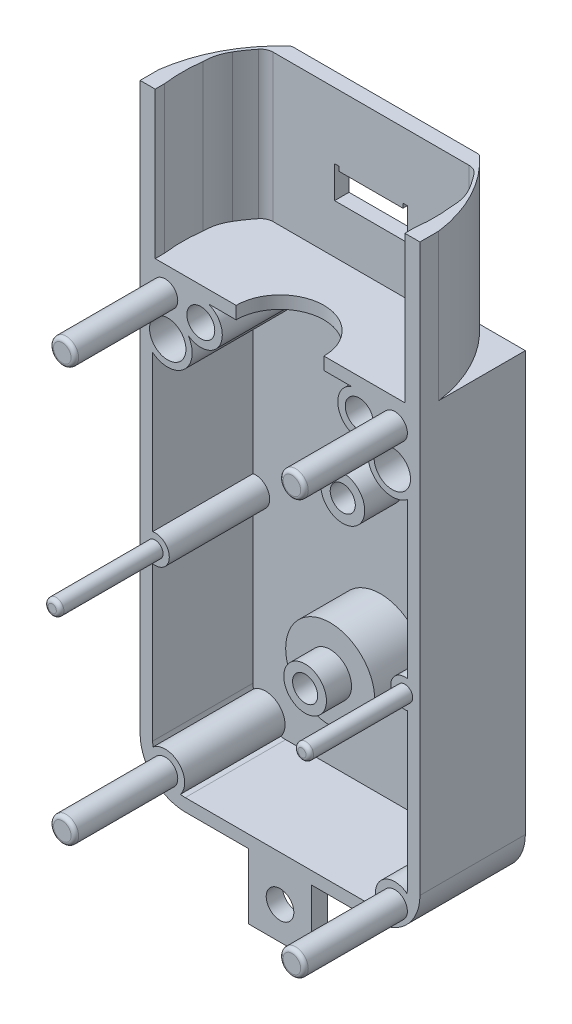
SolidWorks part; units mm, degrees
ref_plane "Front Plane" through (0, 0, 0) normal (0, 0, 1) x (1, 0, 0)
ref_plane "Top Plane" through (0, 0, 0) normal (0, 1, 0) x (1, 0, 0)
ref_plane "Right Plane" through (0, 0, 0) normal (1, 0, 0) x (0, 0, -1)
sketch "Sketch1" plane through (0, 0, 0) normal (0, 0, 1) x (1, 0, 0)
  line L0 (-9.95, -18.5) -> (-9.95, -1.55) construction
  line L1 (-7.55, -18.5) -> (7.55, -18.5)
  line L2 (-11.15, -14.9) -> (-11.15, 18.5)
  line L3 (-11.15, 18.5) -> (11.15, 18.5)
  line L4 (11.15, -14.9) -> (11.15, 18.5)
  line L5 (-11.15, -18.5) -> (11.15, 18.5) construction
  line L6 (-11.15, 18.5) -> (11.15, -18.5) construction
  line L7 (9.15, -18.5) -> (9.15, -16.5) construction
  line L8 (0, -18.5) -> (0, -7.2) construction
  line L9 (0, 0) -> (5.3483, 0)
  line L10 (8.95, 13.4566) -> (11.15, 13.4566)
  circle A0 centre (9.15, -16.5) radius 1
  circle A1 centre (-9.95, -1.55) radius 0.625
  circle A2 centre (9.95, -1.55) radius 0.625
  circle A3 centre (-9.15, -16.5) radius 1
  circle A4 centre (0, -7.2) radius 2.7
  circle A5 centre (9.15, 16.5) radius 1
  circle A6 centre (-9.15, 16.5) radius 1
  circle A7 centre (8.95, 13.4566) radius 1.45
  circle A8 centre (6.3127, 15.9) radius 1.1123
  circle A9 centre (-6.3127, 15.9) radius 1.1123
  circle A10 centre (-8.95, 13.4566) radius 1.45
  arc A11 (-11.15, -14.9) -> (-7.55, -18.5) centre (-7.55, -14.9) ccw
  arc A12 (11.15, -14.9) -> (7.55, -18.5) centre (7.55, -14.9) cw
  point P0 (0, 0)
  dimension "D7" = 2
  dimension "D8" = 1.25
  dimension "D10" = 5.4
  dimension "D12" = 2.9
  dimension "D13" = 2
  dimension "D17" = 3.6
  dimension "D1" = 22.3
  dimension "D2" = 37
  dimension "D3" = 16.95
  dimension "D4" = 1.2
  dimension "D5" = 2
  dimension "D6" = 2
  dimension "D9" = 11.3
  dimension "D11" = 2.2
  dimension "D14" = 3.05
  dimension "D15" = 2.6
  dimension "D16" = 2.9
extrude "Boss-Extrude1" add sketch "Sketch1" along normal blind 1 contours A12 L4 A7 L3 L2 A11 L1 A9 A8 A6 A3 A0 A1 A2 A4 A5 A10 region at (0, -0.045, 0)
sketch "Sketch2" plane through (0, 0, 0) normal (0, 0, 1) x (1, 0, 0)
  line L0 (0, 18.5) -> (0, 11.4842) construction
  line L1 (-11.15, 18.5) -> (11.15, 18.5) construction
  line L2 (-11.15, -14.9) -> (-11.15, 18.5) construction
  line L3 (11.15, -14.9) -> (11.15, 18.5) construction
  line L4 (-7.55, -18.5) -> (7.55, -18.5) construction
  line L5 (-11.15, -14.9) -> (-11.15, 18.5)
  line L6 (-11.15, 18.5) -> (11.15, 18.5)
  line L7 (11.15, -14.9) -> (11.15, 18.5)
  line L8 (-7.55, -18.5) -> (7.55, -18.5)
  line L9 (-10.15, -14.9) -> (-10.15, -2.6571)
  line L10 (-10.15, -0.4429) -> (-10.15, 11.9195)
  line L11 (10.15, -14.9) -> (10.15, -2.6571)
  line L12 (-7.55, -17.5) -> (7.55, -17.5)
  line L13 (10.15, -14.9) -> (10.15, 17.5) construction
  line L14 (-10.15, -14.9) -> (-10.15, 17.5) construction
  line L15 (-5.7028, 17.5) -> (5.7028, 17.5)
  line L16 (-10.15, 17.5) -> (10.15, 17.5) construction
  line L17 (10.15, -0.4429) -> (10.15, 11.9195)
  arc A0 (-7.9413, -17.4704) -> (-10.1204, -15.2913) centre (-9.15, -16.5) ccw
  circle A1 centre (-6.3127, 15.9) radius 1.1123 construction
  circle A2 centre (-6.3127, 15.9) radius 1.7123
  arc A3 (-7.3059, 14.5051) -> (-5.7028, 17.5) centre (-6.3127, 15.9) ccw
  circle A4 centre (-6.3127, 15.9) radius 1.1123
  circle A5 centre (-8.95, 13.4566) radius 1.45 construction
  circle A6 centre (-8.95, 13.4566) radius 1.45
  arc A7 (-10.15, 11.9195) -> (-7.3059, 14.5051) centre (-8.95, 13.4566) ccw
  circle A8 centre (-9.95, -1.55) radius 0.625 construction
  circle A9 centre (-9.95, -1.55) radius 0.625
  arc A10 (-10.15, -2.6571) -> (-10.15, -0.4429) centre (-9.95, -1.55) ccw
  circle A11 centre (-9.15, -16.5) radius 1 construction
  circle A12 centre (-9.15, -16.5) radius 1
  circle A13 centre (9.15, -16.5) radius 1
  circle A15 centre (9.95, -1.55) radius 0.625
  arc A16 (10.15, -2.6571) -> (10.15, -0.4429) centre (9.95, -1.55) cw
  circle A17 centre (8.95, 13.4566) radius 1.45
  arc A18 (10.15, 11.9195) -> (7.3059, 14.5051) centre (8.95, 13.4566) cw
  circle A19 centre (6.3127, 15.9) radius 1.1123
  arc A20 (7.3059, 14.5051) -> (5.7028, 17.5) centre (6.3127, 15.9) cw
  arc A21 (7.55, -18.5) -> (11.15, -14.9) centre (7.55, -14.9) ccw construction
  arc A22 (-11.15, -14.9) -> (-7.55, -18.5) centre (-7.55, -14.9) ccw construction
  arc A23 (7.55, -18.5) -> (11.15, -14.9) centre (7.55, -14.9) ccw
  arc A24 (-11.15, -14.9) -> (-7.55, -18.5) centre (-7.55, -14.9) ccw
  arc A25 (7.55, -17.5) -> (7.9413, -17.4704) centre (7.55, -14.9) ccw
  arc A26 (-10.15, -14.9) -> (-10.1204, -15.2913) centre (-7.55, -14.9) ccw
  circle A27 centre (-8.95, 13.4566) radius 1.95 construction
  circle A28 centre (-9.15, 16.5) radius 1 construction
  circle A29 centre (-9.15, 16.5) radius 1
  circle A30 centre (9.15, 16.5) radius 1 construction
  circle A31 centre (9.15, 16.5) radius 1
  circle A32 centre (-9.95, -1.55) radius 1.125 construction
  circle A33 centre (-9.15, -16.5) radius 1.55 construction
  arc A34 (-7.9413, -17.4704) -> (-7.55, -17.5) centre (-7.55, -14.9) ccw
  arc A35 (-10.15, -14.9) -> (-7.55, -17.5) centre (-7.55, -14.9) ccw construction
  arc A36 (10.1204, -15.2913) -> (10.15, -14.9) centre (7.55, -14.9) ccw
  arc A37 (7.55, -17.5) -> (10.15, -14.9) centre (7.55, -14.9) ccw construction
  arc A38 (7.9413, -17.4704) -> (10.1204, -15.2913) centre (9.15, -16.5) cw
  dimension "D1" = 0.6
  dimension "D2" = 0.5
  dimension "D3" = 0.5
  dimension "D4" = 0.55
  dimension "D5" = 1
extrude "Boss-Extrude2" add sketch "Sketch2" along normal blind 9.9
sketch "Sketch3" plane through (0, 0, 1) normal (0, 0, 1) x (1, 0, 0)
  line L0 (5.7028, 17.5) -> (-5.7028, 17.5) construction
  line L1 (5.7028, 17.5) -> (4.3272, 17.5)
  line L2 (-4.3272, 17.5) -> (-5.7028, 17.5)
  arc A0 (-7, 13.4444) -> (-4.3272, 17.5) centre (-6.3127, 15.9) ccw
  arc A1 (4.3272, 17.5) -> (7, 13.4444) centre (6.3127, 15.9) ccw
  arc A2 (-7.3059, 14.5051) -> (-5.7028, 17.5) centre (-6.3127, 15.9) ccw construction
  arc A3 (-7.3059, 14.5051) -> (-5.7028, 17.5) centre (-6.3127, 15.9) ccw
  arc A4 (-10.15, 11.9195) -> (-7.3059, 14.5051) centre (-8.95, 13.4566) ccw construction
  arc A5 (-7, 13.4444) -> (-7.3059, 14.5051) centre (-8.95, 13.4566) ccw
  arc A6 (5.7028, 17.5) -> (7.3059, 14.5051) centre (6.3127, 15.9) ccw construction
  arc A7 (5.7028, 17.5) -> (7.3059, 14.5051) centre (6.3127, 15.9) ccw
  arc A8 (7.3059, 14.5051) -> (10.15, 11.9195) centre (8.95, 13.4566) ccw construction
  arc A9 (7.3059, 14.5051) -> (7, 13.4444) centre (8.95, 13.4566) ccw
  dimension "D1" = 5.1
  dimension "D2" = 5.1
extrude "Boss-Extrude3" add sketch "Sketch3" along normal blind 1.55
sketch "Sketch4" plane through (0, 0, 0) normal (0, 0, -1) x (-1, 0, 0)
  line L0 (0, 18.5) -> (0, 14.3921) construction
  line L1 (11.15, 18.5) -> (-11.15, 18.5) construction
  circle A0 centre (-6.3127, 15.9) radius 2.2
  circle A1 centre (6.3127, 15.9) radius 2.2
  dimension "D1" = 4.4
extrude "Cut-Extrude1" cut sketch "Sketch4" against normal blind 2.1
sketch "Sketch5" plane through (0, 0, 0) normal (0, 0, -1) x (-1, 0, 0)
  circle A0 centre (0, -7.2) radius 3.55
  circle A1 centre (0, -7.2) radius 2.7 construction
  circle A2 centre (0, -7.2) radius 2.7
  dimension "D1" = 7.1
extrude "Boss-Extrude4" add sketch "Sketch5" along normal blind 0.8
sketch "Sketch6" plane through (0, 0, 0) normal (0, 0, -1) x (-1, 0, 0)
  circle A0 centre (0, 4.45) radius 2.05
extrude "Boss-Extrude5" add sketch "Sketch6" along normal blind 2.4
sketch "Sketch7" plane through (0, 0, 9.9) normal (0, 0, 1) x (1, 0, 0)
  line L0 (-7.55, -18.5) -> (7.55, -18.5) construction
  line L1 (-2.5, -18.5) -> (2.5, -18.5)
  line L3 (-2.5, -18.5) -> (-2.5, -23.7)
  line L4 (-2.5, -23.7) -> (2.5, -23.7)
  line L5 (2.5, -18.5) -> (2.5, -23.7)
  circle A0 centre (0, -21.1) radius 1.1
  point P0 (0, -18.5)
  point P1 (0, -18.5)
  dimension "D2" = 2.2
  dimension "D1" = 5
extrude "Boss-Extrude6" add sketch "Sketch7" against normal blind 1.3
sketch "Sketch8" plane through (0, 18.5, 0) normal (0, 1, 0) x (1, 0, 0)
  line L0 (11.15, -9.9) -> (-11.15, -9.9) construction
  line L1 (3.5, -9.9) -> (-3.5, -9.9)
  arc A0 (3.5, -9.9) -> (-3.5, -9.9) centre (0, -9.9) ccw
  dimension "D1" = 7
extrude "Cut-Extrude2" cut sketch "Sketch8" against normal blind 1.3
sketch "Sketch9" plane through (0, 18.5, 0) normal (0, 1, 0) x (1, 0, 0)
  line L0 (-2.5, -9.9) -> (2.5, -9.9) construction
  line L1 (-9.95, -9.9) -> (-9.95, -9.1592)
  line L2 (9.95, -9.9) -> (9.95, -9.1592)
  line L3 (11.15, -9.9) -> (3.5, -9.9) construction
  line L4 (7.4835, -1.5) -> (-7.4835, -1.5)
  line L5 (0, -9.9) -> (0, -4.9263) construction
  line L6 (11.15, -9.9) -> (9.95, -9.9)
  line L7 (-9.95, -9.9) -> (-11.15, -9.9)
  line L8 (7.8062, -2.65) -> (-7.8062, -2.65)
  line L9 (11.15, -9.9) -> (11.15, 0) construction
  line L10 (11.15, -9.9) -> (11.15, -8.4033)
  line L11 (-11.15, -9.9) -> (-11.15, 0) construction
  line L12 (-11.15, -9.9) -> (-11.15, -8.4033)
  arc A0 (11.15, -8.4033) -> (7.4835, -1.5) centre (0, -9.9) ccw
  arc A1 (9.4392, -4.2518) -> (8.5869, -3.025) centre (0, -9.9) ccw
  arc A2 (-7.4835, -1.5) -> (-11.15, -8.4033) centre (0, -9.9) ccw
  arc A3 (-8.5869, -3.025) -> (-9.4392, -4.2518) centre (0, -9.9) ccw
  arc A4 (-9.95, -6.1003) -> (-9.4392, -4.2518) centre (-6.35, -6.1003) cw
  arc A5 (9.95, -6.1003) -> (9.4392, -4.2518) centre (6.35, -6.1003) ccw
  arc A6 (-7.8062, -2.65) -> (-8.5869, -3.025) centre (-7.8062, -3.65) ccw
  arc A7 (7.8062, -2.65) -> (8.5869, -3.025) centre (7.8062, -3.65) cw
  arc A8 (9.95, -9.1592) -> (9.95, -6.1003) centre (-2.0177, -7.6298) ccw
  arc A9 (-9.95, -9.1592) -> (-9.95, -6.1003) centre (2.0177, -7.6298) cw
  point P2 (0, -9.9)
  point P28 (-8.2727, -2.65)
  dimension "D3" = 1.2
  dimension "D2" = 22
  dimension "D4" = 3.6
  dimension "D5" = 1
  dimension "D6" = 24.13
  dimension "D1" = 0
extrude "Boss-Extrude7" add sketch "Sketch9" along normal blind 11.7
sketch "Sketch10" plane through (0, 0, 2.65) normal (0, 0, 1) x (1, 0, 0)
  line L2 (0, 24.6) -> (0, 22.4) construction
  line L3 (2.55, 24.6) -> (-2.55, 24.6)
  line L4 (2.9, 24.6) -> (2.9, 22.4)
  line L5 (2.9, 22.4) -> (-2.9, 22.4)
  line L6 (-2.9, 24.6) -> (-2.9, 22.4)
  line L7 (2.9, 24.6) -> (-2.9, 22.4) construction
  line L8 (2.9, 22.4) -> (-2.9, 24.6) construction
  line L10 (2.55, 24.6) -> (2.55, 24.95)
  line L12 (-2.55, 24.6) -> (-2.55, 24.95)
  line L13 (2.55, 24.0735) -> (0, 24.6) construction
  line L15 (-2.9, 24.95) -> (-2.55, 24.95)
  line L17 (-2.9, 24.95) -> (-2.9, 24.6)
  line L18 (2.9, 24.95) -> (2.9, 24.6)
  line L19 (2.55, 24.95) -> (2.9, 24.95)
  line L20 (0, 24.6) -> (-2.55, 24.0735) construction
  point P0 (0, 23.5)
extrude "Cut-Extrude3" cut sketch "Sketch10" against normal blind 1.7
sketch "Sketch11" plane through (0, 0, 1.5) normal (0, 0, -1) x (-1, 0, 0)
  line L1 (2.55, 24.6) -> (-2.55, 24.6)
  line L2 (2.55, 24.6) -> (2.55, 26.2)
  line L3 (2.55, 26.2) -> (-2.55, 26.2)
  line L4 (-2.55, 24.6) -> (-2.55, 26.2)
  dimension "D1" = 1.6
extrude "Boss-Extrude8" add sketch "Sketch11" along normal blind 3
sketch "Sketch12" plane through (0, 26.2, 0) normal (0, 1, 0) x (1, 0, 0)
  line L0 (-2.55, 1.5) -> (-2.55, -1.5) construction
  line L1 (2.55, 1.5) -> (-2.55, 1.5)
  line L2 (2.55, 1.5) -> (2.55, 0.5)
  line L3 (2.55, 0.5) -> (-2.55, 0.5)
  line L4 (-2.55, 1.5) -> (-2.55, 0.5)
  dimension "D1" = 1
extrude "Boss-Extrude9" add sketch "Sketch12" against normal blind 2.5
sketch "Sketch13" plane through (0, 0, 1) normal (0, 0, 1) x (1, 0, 0)
  circle A2 centre (0, 4.45) radius 1
  dimension "D1" = 2
extrude "Cut-Extrude4" cut sketch "Sketch13" against normal blind 2.5
fillet "Fillet1" radius 0.3 1 edges at (-2.05, 4.45, -2.4)
fillet "Fillet2" radius 0.3 2 edges at (7.4835, 24.35, 1.5) (-7.4835, 24.35, 1.5)
sketch "Sketch15" plane through (-10.15, 0, 0) normal (1, 0, 0) x (0, 0, -1)
  line L0 (-9.9, -8.7785) -> (-1.9, -8.7785)
  line L1 (-9.9, -2.6571) -> (-9.9, -14.9) construction
  dimension "D1" = 8
sketch "Sketch16" plane through (0, 0, 1) normal (0, 0, 1) x (1, 0, 0)
  line L6 (4.3272, 17.5) -> (-4.3272, 17.5)
  line L7 (-10.15, 11.9195) -> (-10.15, -0.4429)
  line L8 (-10.15, -2.6571) -> (-10.15, -14.9)
  line L9 (-7.55, -17.5) -> (7.55, -17.5)
  line L10 (10.15, -14.9) -> (10.15, -2.6571)
  line L11 (10.15, -0.4429) -> (10.15, 11.9195)
  line L12 (4.3272, 17.5) -> (-4.3272, 17.5)
  line L13 (-10.15, 11.9195) -> (-10.15, -0.4429)
  line L14 (-10.15, -2.6571) -> (-10.15, -14.9)
  line L15 (-7.55, -17.5) -> (7.55, -17.5)
  line L16 (10.15, -14.9) -> (10.15, -2.6571)
  line L17 (10.15, -0.4429) -> (10.15, 11.9195)
  arc A12 (-7, 13.4444) -> (-4.3272, 17.5) centre (-6.3127, 15.9) ccw
  arc A13 (-10.15, 11.9195) -> (-7, 13.4444) centre (-8.95, 13.4566) ccw
  arc A14 (-10.15, -2.6571) -> (-10.15, -0.4429) centre (-9.95, -1.55) ccw
  arc A15 (-10.15, -14.9) -> (-10.1204, -15.2913) centre (-7.55, -14.9) ccw
  arc A16 (-7.9413, -17.4704) -> (-10.1204, -15.2913) centre (-9.15, -16.5) ccw
  arc A17 (-7.9413, -17.4704) -> (-7.55, -17.5) centre (-7.55, -14.9) ccw
  arc A18 (7.55, -17.5) -> (7.9413, -17.4704) centre (7.55, -14.9) ccw
  arc A19 (10.1204, -15.2913) -> (7.9413, -17.4704) centre (9.15, -16.5) ccw
  arc A20 (10.1204, -15.2913) -> (10.15, -14.9) centre (7.55, -14.9) ccw
  arc A21 (10.15, -0.4429) -> (10.15, -2.6571) centre (9.95, -1.55) ccw
  arc A22 (7, 13.4444) -> (10.15, 11.9195) centre (8.95, 13.4566) ccw
  arc A23 (4.3272, 17.5) -> (7, 13.4444) centre (6.3127, 15.9) ccw
  arc A24 (-7, 13.4444) -> (-4.3272, 17.5) centre (-6.3127, 15.9) ccw
  arc A25 (-10.15, 11.9195) -> (-7, 13.4444) centre (-8.95, 13.4566) ccw
  arc A26 (-10.15, -2.6571) -> (-10.15, -0.4429) centre (-9.95, -1.55) ccw
  arc A27 (-10.15, -14.9) -> (-10.1204, -15.2913) centre (-7.55, -14.9) ccw
  arc A28 (-7.9413, -17.4704) -> (-10.1204, -15.2913) centre (-9.15, -16.5) ccw
  arc A29 (-7.9413, -17.4704) -> (-7.55, -17.5) centre (-7.55, -14.9) ccw
  arc A30 (7.55, -17.5) -> (7.9413, -17.4704) centre (7.55, -14.9) ccw
  arc A31 (10.1204, -15.2913) -> (7.9413, -17.4704) centre (9.15, -16.5) ccw
  arc A32 (10.1204, -15.2913) -> (10.15, -14.9) centre (7.55, -14.9) ccw
  arc A33 (10.15, -0.4429) -> (10.15, -2.6571) centre (9.95, -1.55) ccw
  arc A34 (7, 13.4444) -> (10.15, 11.9195) centre (8.95, 13.4566) ccw
  arc A35 (4.3272, 17.5) -> (7, 13.4444) centre (6.3127, 15.9) ccw
  dimension "D1" = 0
extrude "Boss-Extrude10" add sketch "Sketch16" along normal up to vertex (0.9 mm away) up to point (-10.15, -8.7785, 1.9)
sketch "Sketch17" plane through (0, 0, 2.1) normal (0, 0, -1) x (-1, 0, 0)
  arc A4 (8.2517, 16.9394) -> (8.5065, 15.7345) centre (9.15, 16.5) ccw
  arc A5 (8.2517, 16.9394) -> (7.7012, 14.1935) centre (6.3127, 15.9) ccw
  arc A6 (8.1201, 14.6456) -> (7.7012, 14.1935) centre (8.95, 13.4566) ccw
  arc A7 (8.1201, 14.6456) -> (8.5065, 15.7345) centre (6.3127, 15.9) ccw
  arc A8 (8.2517, 16.9394) -> (8.5065, 15.7345) centre (9.15, 16.5) ccw
  arc A9 (8.2517, 16.9394) -> (7.7012, 14.1935) centre (6.3127, 15.9) ccw
  arc A10 (8.1201, 14.6456) -> (7.7012, 14.1935) centre (8.95, 13.4566) ccw
  arc A11 (8.1201, 14.6456) -> (8.5065, 15.7345) centre (6.3127, 15.9) ccw
  arc A12 (-8.5065, 15.7345) -> (-8.2517, 16.9394) centre (-9.15, 16.5) ccw
  arc A13 (-8.5065, 15.7345) -> (-8.1201, 14.6456) centre (-6.3127, 15.9) ccw
  arc A14 (-7.7012, 14.1935) -> (-8.1201, 14.6456) centre (-8.95, 13.4566) ccw
  arc A15 (-7.7012, 14.1935) -> (-8.2517, 16.9394) centre (-6.3127, 15.9) ccw
  arc A16 (-8.5065, 15.7345) -> (-8.2517, 16.9394) centre (-9.15, 16.5) ccw
  arc A17 (-8.5065, 15.7345) -> (-8.1201, 14.6456) centre (-6.3127, 15.9) ccw
  arc A18 (-7.7012, 14.1935) -> (-8.1201, 14.6456) centre (-8.95, 13.4566) ccw
  arc A19 (-7.7012, 14.1935) -> (-8.2517, 16.9394) centre (-6.3127, 15.9) ccw
  dimension "D1" = 0
  dimension "D2" = 0
extrude "Boss-Extrude11" add sketch "Sketch17" along normal up to vertex up to point (-7.7012, 14.1935, 0)
sketch "Sketch18" plane through (0, 0, 2.55) normal (0, 0, 1) x (1, 0, 0)
  line L1 (-4.3272, 17.5) -> (-5.7028, 17.5)
  line L2 (-4.3272, 17.5) -> (-5.7028, 17.5)
  line L3 (5.7028, 17.5) -> (4.3272, 17.5)
  line L4 (5.7028, 17.5) -> (4.3272, 17.5)
  arc A3 (-7.3059, 14.5051) -> (-5.7028, 17.5) centre (-6.3127, 15.9) ccw
  arc A4 (-7, 13.4444) -> (-7.3059, 14.5051) centre (-8.95, 13.4566) ccw
  arc A5 (-7, 13.4444) -> (-4.3272, 17.5) centre (-6.3127, 15.9) ccw
  arc A6 (-7.3059, 14.5051) -> (-5.7028, 17.5) centre (-6.3127, 15.9) ccw
  arc A7 (-7, 13.4444) -> (-7.3059, 14.5051) centre (-8.95, 13.4566) ccw
  arc A8 (-7, 13.4444) -> (-4.3272, 17.5) centre (-6.3127, 15.9) ccw
  arc A9 (4.3272, 17.5) -> (7, 13.4444) centre (6.3127, 15.9) ccw
  arc A10 (7.3059, 14.5051) -> (7, 13.4444) centre (8.95, 13.4566) ccw
  arc A11 (5.7028, 17.5) -> (7.3059, 14.5051) centre (6.3127, 15.9) ccw
  arc A12 (4.3272, 17.5) -> (7, 13.4444) centre (6.3127, 15.9) ccw
  arc A13 (7.3059, 14.5051) -> (7, 13.4444) centre (8.95, 13.4566) ccw
  arc A14 (5.7028, 17.5) -> (7.3059, 14.5051) centre (6.3127, 15.9) ccw
  dimension "D1" = 0
  dimension "D2" = 0
extrude "Cut-Extrude5" cut sketch "Sketch18" against normal up to vertex up to point (-7, 13.4444, 1.9)
sketch "Sketch19" plane through (0, 18.5, 0) normal (0, 1, 0) x (1, 0, 0)
  line L0 (11.15, -8.4033) -> (11.15, 0) construction
  line L1 (-11.15, 3.5146) -> (11.15, 3.5146)
  line L2 (-11.15, 3.5146) -> (-11.15, -1.5)
  line L3 (-11.15, -1.5) -> (11.15, -1.5)
  line L4 (11.15, 3.5146) -> (11.15, -1.5)
extrude "Cut-Extrude7" cut sketch "Sketch19" against normal blind 37.5
sketch "Sketch20" plane through (0, 0, 1.5) normal (0, 0, -1) x (-1, 0, 0)
  circle A1 centre (0, -7.2) radius 2.7
  circle A2 centre (0, -7.2) radius 2.7
  circle A3 centre (0, -7.2) radius 3.55
  circle A4 centre (0, -7.2) radius 3.55
  dimension "D1" = 0
  dimension "D2" = 0
extrude "Boss-Extrude12" add sketch "Sketch20" against normal blind 4.4
sketch "Sketch21" plane through (0, 0, 1.5) normal (0, 0, -1) x (-1, 0, 0)
  circle A3 centre (0, -7.2) radius 2.7
  circle A4 centre (0, -7.2) radius 2.7
  dimension "D2" = 0
extrude "Cut-Extrude8" cut sketch "Sketch21" against normal blind 3.4
sketch "Sketch22" plane through (0, 0, 5.9) normal (0, 0, 1) x (1, 0, 0)
  circle A0 centre (0, -7.2) radius 1
  circle A1 centre (0, -7.2) radius 2.7 construction
  circle A2 centre (0, -7.2) radius 2.7
  dimension "D1" = 2
extrude "Boss-Extrude13" add sketch "Sketch22" against normal blind 1
sketch "Sketch23" plane through (0, 0, 5.9) normal (0, 0, 1) x (1, 0, 0)
  circle A0 centre (0, -7.2) radius 1 construction
  circle A1 centre (0, -7.2) radius 1
  circle A2 centre (0, -7.2) radius 1.7
  dimension "D1" = 3.4
extrude "Boss-Extrude14" add sketch "Sketch23" along normal blind 2
sketch "Sketch24" plane through (0, 0, 1.9) normal (0, 0, 1) x (1, 0, 0)
  circle A0 centre (0, 4.45) radius 1.75
  circle A1 centre (0, 4.45) radius 1
  circle A2 centre (0, 4.45) radius 1
  dimension "D2" = 3.5
  dimension "D1" = 0
extrude "Boss-Extrude15" add sketch "Sketch24" along normal blind 3
ref_plane "Plane1" through (0, 0, 8.9) normal (0, 0, 1) x (1, 0, 0)
sketch "Sketch26" plane through (0, 0, 8.9) normal (0, 0, 1) x (1, 0, 0)
  circle A0 centre (-9.15, 16.5) radius 1 construction
  circle A1 centre (-9.15, 16.5) radius 1
  circle A2 centre (9.15, 16.5) radius 1 construction
  circle A3 centre (9.15, 16.5) radius 1
  circle A4 centre (-9.95, -1.55) radius 0.625 construction
  circle A5 centre (-9.95, -1.55) radius 0.625
  circle A6 centre (9.95, -1.55) radius 0.625 construction
  circle A7 centre (9.95, -1.55) radius 0.625
  circle A8 centre (-9.15, -16.5) radius 1 construction
  circle A9 centre (-9.15, -16.5) radius 1
  circle A10 centre (9.15, -16.5) radius 1 construction
  circle A11 centre (9.15, -16.5) radius 1
extrude "Boss-Extrude16" add sketch "Sketch26" along normal blind 9.2
fillet "Fillet3" radius 0.3 6 edges at (10.15, -16.5, 18.1) (-8.15, -16.5, 18.1) (10.575, -1.55, 18.1) (-9.325, -1.55, 18.1) (10.15, 16.5, 18.1) (-8.15, 16.5, 18.1)
fillet "Fillet4" radius 0.5 1 edges at (-2.7, -7.2, 1.5)
